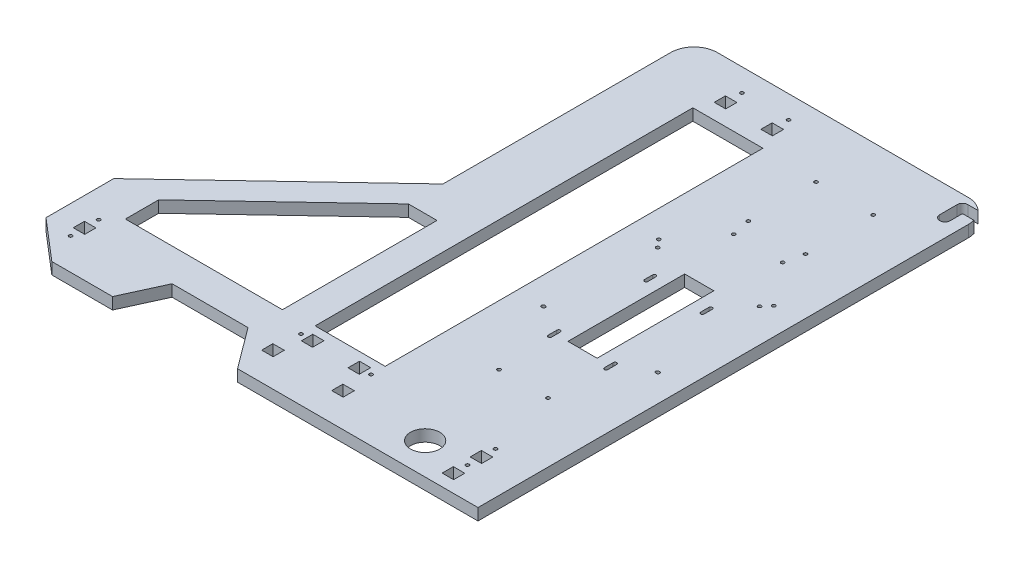
SolidWorks part; units mm, degrees
ref_plane "Front Plane" through (0, 0, 0) normal (0, 0, 1) x (1, 0, 0)
ref_plane "Top Plane" through (0, 0, 0) normal (0, 1, 0) x (1, 0, 0)
ref_plane "Right Plane" through (0, 0, 0) normal (1, 0, 0) x (0, 0, -1)
sketch "Sketch1" plane through (0, 0, 0) normal (0, 1, 0) x (1, 0, 0)
  line L0 (0, 0) -> (-235, 0)
  line L1 (-235, 0) -> (-235, -215)
  line L2 (-235, -215) -> (-380, -352)
  line L3 (-380, -352) -> (-380, -410)
  line L4 (-380, -410) -> (-345, -440)
  line L5 (-345, -440) -> (-293, -440)
  line L6 (-293, -440) -> (-277, -405)
  line L7 (-277, -405) -> (-212, -405)
  line L8 (-212, -405) -> (-185.9255, -440)
  line L9 (-185.9255, -440) -> (0, -440)
  line L10 (0, 0) -> (0, -440)
  line L12 (-293, -440) -> (-185.9255, -440) construction
  dimension "D3" = 235
  dimension "D5" = 58
  dimension "D13" = 190
  dimension "D7" = 35
  dimension "D2" = 126.686
  dimension "D11" = 65
  dimension "D15" = 52
  dimension "D12" = 30
  dimension "D10" = 35
  dimension "D14" = 16
  dimension "D6" = 380
  dimension "D4" = 440
extrude "Boss-Extrude1" add sketch "Sketch1" along normal blind 10
sketch "Sketch16" plane through (0, 10, 0) normal (0, 1, 0) x (1, 0, 0)
  line L0 (0, -440) -> (20, -440)
  line L1 (20, -440) -> (20, 0)
  line L2 (20, 0) -> (0, 0)
  line L3 (0, 0) -> (0, -440)
  dimension "D1" = 20
  dimension "D2" = 90
extrude "Boss-Extrude2" add sketch "Sketch16" against normal through all
sketch "Sketch2" plane through (0, 10, 0) normal (0, 1, 0) x (1, 0, 0)
  line L0 (-235, -215) -> (-235, -405) construction
  line L1 (-277, -405) -> (-212, -405) construction
  line L2 (-345, -440) -> (-345, -318.931) construction
  line L3 (-235, -215) -> (-380, -352) construction
  line L4 (-345, -348.5097) -> (-235, -244.5787)
  line L5 (-235, -244.5787) -> (-210.5, -244.5787)
  line L6 (-210.5, -244.5787) -> (-210.5, -377)
  line L7 (-210.5, -377) -> (-345, -377)
  line L8 (-345, -377) -> (-345, -348.5097)
  line L9 (0, -440) -> (0, 0) construction
  line L10 (-184.5, -375) -> (-124.5, -375)
  line L11 (-184.5, -375) -> (-184.5, -51.45)
  line L12 (-184.5, -51.45) -> (-124.5, -51.45)
  line L13 (-124.5, -375) -> (-124.5, -51.45)
  line L14 (-124.5, -387.1) -> (-184.5, -387.1) construction
  line L15 (-16, -440) -> (-16, 0) construction
  line L16 (20, 0) -> (-235, 0) construction
  line L17 (-355.95, -430.6143) -> (-355.95, -329.2769) construction
  line L18 (-20.9, -429.8) -> (-11.1, -429.8)
  line L19 (-20.9, -429.8) -> (-20.9, -420.2)
  line L20 (-20.9, -420.2) -> (-11.1, -420.2)
  line L21 (-11.1, -429.8) -> (-11.1, -420.2)
  line L22 (-20.9, -429.8) -> (-11.1, -420.2) construction
  line L23 (-20.9, -420.2) -> (-11.1, -429.8) construction
  line L24 (-20.9, -405.8) -> (-11.1, -405.8)
  line L25 (-20.9, -405.8) -> (-20.9, -396.2)
  line L26 (-20.9, -396.2) -> (-11.1, -396.2)
  line L27 (-11.1, -405.8) -> (-11.1, -396.2)
  line L28 (-20.9, -405.8) -> (-11.1, -396.2) construction
  line L29 (-20.9, -396.2) -> (-11.1, -405.8) construction
  line L30 (-380, -410) -> (-345, -440) construction
  line L32 (-351.05, -396.2) -> (-360.85, -396.2)
  line L33 (-351.05, -396.2) -> (-351.05, -405.8)
  line L34 (-351.05, -405.8) -> (-360.85, -405.8)
  line L35 (-360.85, -396.2) -> (-360.85, -405.8)
  line L36 (-351.05, -396.2) -> (-360.85, -405.8) construction
  line L37 (-351.05, -405.8) -> (-360.85, -396.2) construction
  line L38 (-185.9255, -440) -> (20, -440) construction
  line L39 (-185.9255, -440) -> (20, -440) construction
  line L40 (-173.724, -33.45) -> (-113.724, -33.45) construction
  line L41 (-154.5, -51.45) -> (-154.5, -33.45) construction
  line L42 (-179.4, -28.65) -> (-169.6, -28.65)
  line L43 (-179.4, -28.65) -> (-179.4, -38.25)
  line L44 (-179.4, -38.25) -> (-169.6, -38.25)
  line L45 (-169.6, -28.65) -> (-169.6, -38.25)
  line L46 (-179.4, -28.65) -> (-169.6, -38.25) construction
  line L47 (-179.4, -38.25) -> (-169.6, -28.65) construction
  line L48 (-129.6, -38.25) -> (-139.4, -28.65) construction
  line L49 (-129.6, -28.65) -> (-139.4, -38.25) construction
  line L50 (-139.4, -28.65) -> (-139.4, -38.25)
  line L51 (-129.6, -38.25) -> (-139.4, -38.25)
  line L52 (-129.6, -28.65) -> (-129.6, -38.25)
  line L53 (-129.6, -28.65) -> (-139.4, -28.65)
  line L54 (-174.5, -33.45) -> (-174.5, -19.45) construction
  line L55 (-134.5, -33.45) -> (-134.5, -19.45) construction
  line L56 (-154.5, -375) -> (-154.5, -440) construction
  line L57 (-174.5, -387.1) -> (-134.5, -387.1) construction
  line L58 (-129.7, -392) -> (-139.3, -382.2) construction
  line L59 (-179.3, -382.2) -> (-169.7, -382.2)
  line L60 (-179.3, -382.2) -> (-179.3, -392)
  line L61 (-179.3, -392) -> (-169.7, -392)
  line L62 (-169.7, -382.2) -> (-169.7, -392)
  line L63 (-179.3, -382.2) -> (-169.7, -392) construction
  line L64 (-179.3, -392) -> (-169.7, -382.2) construction
  line L65 (-129.7, -382.2) -> (-139.3, -392) construction
  line L66 (-139.3, -382.2) -> (-139.3, -392)
  line L67 (-129.7, -392) -> (-139.3, -392)
  line L68 (-129.7, -382.2) -> (-129.7, -392)
  line L69 (-129.7, -382.2) -> (-139.3, -382.2)
  line L70 (-119.6, -415.9) -> (-129.4, -406.3) construction
  line L71 (-189.4, -406.3) -> (-179.6, -406.3)
  line L72 (-189.4, -406.3) -> (-189.4, -415.9)
  line L73 (-189.4, -415.9) -> (-179.6, -415.9)
  line L74 (-179.6, -406.3) -> (-179.6, -415.9)
  line L75 (-189.4, -406.3) -> (-179.6, -415.9) construction
  line L76 (-189.4, -415.9) -> (-179.6, -406.3) construction
  line L77 (-119.6, -406.3) -> (-129.4, -415.9) construction
  line L78 (-129.4, -406.3) -> (-129.4, -415.9)
  line L79 (-119.6, -415.9) -> (-129.4, -415.9)
  line L80 (-119.6, -406.3) -> (-119.6, -415.9)
  line L81 (-119.6, -406.3) -> (-129.4, -406.3)
  line L82 (-360.85, -396.2) -> (-11.1, -396.2) construction
  circle A0 centre (-16, -413) radius 1.45
  circle A1 centre (-16, -389) radius 1.45
  circle A2 centre (-355.95, -413) radius 1.45
  circle A3 centre (-355.95, -389) radius 1.45
  circle A4 centre (-174.5, -19.45) radius 1.45
  circle A5 centre (-134.5, -19.45) radius 1.45
  circle A6 centre (-124.5, -387.1) radius 1.45
  circle A7 centre (-184.5, -387.1) radius 1.45
  point P25 (-16, -425)
  point P30 (-16, -401)
  point P44 (-355.95, -401)
  point P61 (-174.5, -33.45)
  point P72 (-134.5, -33.45)
  point P85 (-174.5, -387.1)
  point P94 (-134.5, -387.1)
  point P95 (-184.5, -411.1)
  point P104 (-124.5, -411.1)
  point P105 (-154.5, -387.1)
  dimension "D13" = 2.9
  dimension "D14" = 2.9
  dimension "D23" = 2.9
  dimension "D24" = 2.9
  dimension "D31" = 2.9
  dimension "D37" = 2.9
  dimension "D1" = 21.5
  dimension "D2" = 28
  dimension "D3" = 24.5
  dimension "D4" = 60
  dimension "D7" = 26
  dimension "D8" = 9.6
  dimension "D9" = 9.8
  dimension "D10" = 9.8
  dimension "D11" = 9.6
  dimension "D12" = 24
  dimension "D15" = 24
  dimension "D19" = 9.8
  dimension "D20" = 9.6
  dimension "D26" = 12
  dimension "D27" = 9.8
  dimension "D28" = 9.6
  dimension "D33" = 9.6
  dimension "D38" = 9.8
  dimension "D39" = 9.6
  dimension "D41" = 24
  dimension "D34" = 30
  dimension "D36" = 12.1
  dimension "D30" = 18
  dimension "D29" = 40
  dimension "D17" = 15
  dimension "D32" = 14
  dimension "D35" = 20
  dimension "D16" = 12
  dimension "D21" = 90
  dimension "D25" = 24
  dimension "D5" = 353.75
  dimension "D22" = 349.75
  dimension "D40" = 30
  dimension "D6" = 65
  dimension "D42" = 0
  dimension "D43" = 0
  dimension "D18" = 16
  dimension "D44" = 9.8
extrude "Cut-Extrude1" cut sketch "Sketch2" against normal through all
fillet "Fillet1" radius 20 2 edges at (-235, 5, 0) (20, 5, 0)
sketch "Sketch11" plane through (0, 10, 0) normal (0, 1, 0) x (1, 0, 0)
  line L0 (-124.5, -213.225) -> (20, -213.225) construction
  line L1 (20, -440) -> (20, -20) construction
  line L3 (-52.25, -213.225) -> (-52.25, -440) construction
  line L6 (-124.5, -375) -> (-124.5, -51.45) construction
  line L8 (-185.9255, -440) -> (20, -440) construction
  circle A0 centre (-52.25, -413) radius 12.5
  circle A1 centre (-16, -413) radius 1.45 construction
  dimension "D1" = 25
  dimension "D2" = 0
  dimension "D3" = 0
extrude "WiringHole" cut sketch "Sketch11" against normal through all
sketch "Sketch9" [suppressed] plane through (0, 10, 0) normal (0, 1, 0) x (1, 0, 0)
  line L0 (-52.25, -400.5) -> (-52.25, 0) construction
  line L1 (0, 0) -> (-215, 0) construction
  line L2 (-124.5, -213.2375) -> (20, -213.2375) construction
  line L3 (-124.5, -375) -> (-124.5, -51.475) construction
  line L4 (-4.75, -124.7375) -> (-4.75, -301.7375) construction
  line L6 (-99.75, -124.7375) -> (-4.75, -124.7375) construction
  line L7 (-4.75, -301.7375) -> (-99.75, -301.7375) construction
  line L8 (-99.75, -301.7375) -> (-99.75, -124.7375) construction
  line L9 (20, -440) -> (20, -20) construction
  circle A0 centre (-52.25, -413) radius 12.5 construction
  circle A1 centre (-99.75, -124.7375) radius 1.45
  circle A2 centre (-4.75, -124.7375) radius 1.45
  circle A3 centre (-4.75, -301.7375) radius 1.45
  circle A4 centre (-99.75, -301.7375) radius 1.45
  dimension "D3" = 2.9
  dimension "D4" = 2.9
  dimension "D1" = 95
  dimension "D2" = 177
  dimension "D5" = 47.5
extrude "MountingHoles-PSU" [suppressed] cut sketch "Sketch9" against normal through all
sketch "Sketch10" plane through (0, 10, 0) normal (0, 1, 0) x (1, 0, 0)
  line L0 (-124.5, -213.225) -> (20, -213.225) construction
  line L1 (20, -440) -> (20, -20) construction
  line L2 (-64.75, -228.225) -> (-39.75, -228.225) construction
  line L3 (-52.25, -213.225) -> (-52.25, 0) construction
  line L7 (-124.5, -375) -> (-124.5, -51.45) construction
  line L8 (-64.75, -278.225) -> (-39.75, -278.225)
  line L9 (-64.75, -278.225) -> (-64.75, -178.225)
  line L10 (-64.75, -178.225) -> (-39.75, -178.225)
  line L11 (-39.75, -278.225) -> (-39.75, -178.225)
  line L12 (-64.75, -278.225) -> (-39.75, -178.225) construction
  line L13 (-64.75, -178.225) -> (-39.75, -278.225) construction
  line L15 (0, 0) -> (-215, 0) construction
  line L17 (-52.25, -213.225) -> (-52.25, -440) construction
  line L18 (-185.9255, -440) -> (20, -440) construction
  line L19 (-64.75, -213.225) -> (-39.75, -213.225) construction
  line L20 (-52.25, -278.225) -> (-52.25, -178.225) construction
  dimension "D1" = 25
  dimension "D2" = 100
  dimension "D3" = 0
  dimension "D4" = 0
  dimension "D5" = 0
  dimension "D6" = 15
extrude "WiringSlot" cut sketch "Sketch10" against normal through all
sketch "CenterLines" plane through (0, 10, 0) normal (0, 1, 0) x (1, 0, 0)
  line L0 (-52.25, -278.225) -> (-52.25, -178.225) construction
  line L1 (-64.75, -278.225) -> (-39.75, -278.225) construction
  line L2 (-39.75, -178.225) -> (-64.75, -178.225) construction
  line L3 (-64.75, -228.225) -> (-39.75, -228.225) construction
  line L4 (-64.75, -178.225) -> (-64.75, -278.225) construction
  line L5 (-39.75, -278.225) -> (-39.75, -178.225) construction
ref_plane "Plane1" through (-52.25, 0, 0) normal (1, 0, 0) x (0, 0, -1)
sketch "Sketch6" plane through (0, 10, 0) normal (0, 1, 0) x (1, 0, 0)
  line L0 (-52.25, -278.225) -> (-52.25, -178.225) construction
  line L1 (-76.35, -237.075) -> (-28.15, -237.075) construction
  line L2 (-28.15, -192.625) -> (-28.15, -275.125) construction
  line L3 (-64.75, -278.225) -> (-39.75, -278.225) construction
  line L4 (-64.75, -245.925) -> (-39.75, -245.925) construction
  line L5 (-39.75, -178.225) -> (-64.75, -178.225) construction
  line L6 (-28.15, -192.625) -> (-28.15, -199.625) construction
  line L7 (-26.7, -192.625) -> (-26.7, -199.625)
  line L8 (-29.6, -192.625) -> (-29.6, -199.625)
  line L9 (-64.75, -228.225) -> (-39.75, -228.225) construction
  line L10 (-64.75, -178.225) -> (-64.75, -278.225) construction
  line L11 (-39.75, -278.225) -> (-39.75, -178.225) construction
  line L12 (-28.15, -282.125) -> (-28.15, -275.125) construction
  line L13 (-29.6, -282.125) -> (-29.6, -275.125)
  line L14 (-76.35, -274.525) -> (-76.35, -199.625) construction
  line L15 (-28.15, -282.125) -> (-28.15, -199.625) construction
  line L16 (-26.7, -282.125) -> (-26.7, -275.125)
  arc A2 (-26.7, -192.625) -> (-29.6, -192.625) centre (-28.15, -192.625) ccw
  arc A3 (-29.6, -199.625) -> (-26.7, -199.625) centre (-28.15, -199.625) ccw
  circle A4 centre (-76.35, -274.525) radius 1.45
  circle A6 centre (-76.35, -199.625) radius 1.45
  arc A8 (-29.6, -282.125) -> (-26.7, -282.125) centre (-28.15, -282.125) ccw
  arc A9 (-26.7, -275.125) -> (-29.6, -275.125) centre (-28.15, -275.125) ccw
  point P20 (-28.15, -196.125)
  point P25 (-28.15, -278.625)
  dimension "D8" = 2.9
  dimension "D12" = 2.9
  dimension "D4" = 1.45
  dimension "D5" = 1.45
  dimension "D11" = 82.5
  dimension "D14" = 74.9
  dimension "D2" = 24.1
  dimension "D3" = 48.2
  dimension "D6" = 8.85
  dimension "D9" = 7
  dimension "D10" = 7
extrude "MountingHoles-RAMPS" cut sketch "Sketch6" against normal through all
mirror "Mirror1" about plane through (-52.25, 0, 0) normal (1, 0, 0) of "MountingHoles-RAMPS"
sketch "Sketch5" plane through (0, 10, 0) normal (0, 1, 0) x (1, 0, 0)
  line L0 (-39.75, -228.225) -> (-64.75, -228.225) construction
  line L3 (-39.75, -278.225) -> (-39.75, -178.225) construction
  line L5 (-64.75, -178.225) -> (-64.75, -278.225) construction
  line L7 (-31.25, -127.725) -> (-73.25, -127.725) construction
  line L8 (-31.25, -328.725) -> (-73.25, -328.725) construction
  line L9 (-52.25, -228.225) -> (-52.25, -127.725) construction
  line L10 (-52.25, -228.225) -> (-52.25, -328.725) construction
  circle A0 centre (-73.25, -127.725) radius 1.45
  circle A1 centre (-31.25, -127.725) radius 1.45
  circle A2 centre (-31.25, -328.725) radius 1.45
  circle A3 centre (-73.25, -328.725) radius 1.45
  point P17 (-52.25, -127.725)
  point P22 (-52.25, -328.725)
  dimension "D2" = 2.9
  dimension "D5" = 2.9
  dimension "D6" = 2.9
  dimension "D7" = 2.9
  dimension "D3" = 201
  dimension "D4" = 100.5
  dimension "D8" = 21
  dimension "D9" = 21
  dimension "D10" = 100.5
extrude "MountingHoles-Melzi" cut sketch "Sketch5" against normal through all
sketch "Sketch13" plane through (0, 0, 0) normal (0, -1, 0) x (-1, 0, 0)
  line L0 (64.75, -213.225) -> (124.5, -213.225) construction
  line L1 (124.5, -375) -> (124.5, -51.45) construction
  line L2 (101.46, -262.74) -> (101.46, -163.71) construction
  line L3 (52.25, -278.225) -> (52.25, -178.225) construction
  line L4 (64.75, -178.225) -> (64.75, -278.225) construction
  line L6 (101.46, -262.74) -> (3.56, -262.74) construction
  circle A0 centre (101.46, -163.71) radius 1.45
  circle A1 centre (101.46, -262.74) radius 1.45
  circle A2 centre (8.62, -170.19) radius 1.45
  circle A3 centre (3.56, -262.74) radius 1.45
  point P11 (101.46, -213.225)
  dimension "D8" = 2.9
  dimension "D6" = 2.9
  dimension "D1" = 2.9
  dimension "D2" = 49.515
  dimension "D3" = 49.21
  dimension "D4" = 6.48
  dimension "D5" = 92.84
  dimension "D7" = 97.9
extrude "Mountingholes-Smoothieboard" cut sketch "Sketch13" against normal through all
mirror "Flipped" about plane through (-52.25, 0, 0) normal (1, 0, 0) of "Mountingholes-Smoothieboard"
sketch "Sketch21" plane through (0, 10, 0) normal (0, 1, 0) x (1, 0, 0)
  line L0 (-52.25, -178.225) -> (-52.25, 0) construction
  line L1 (-39.75, -178.225) -> (-64.75, -178.225) construction
  line L2 (0, 0) -> (-215, 0) construction
  line L3 (-52.25, -82.725) -> (-23.3697, -82.725) construction
  circle A0 centre (-27.75, -53.725) radius 1.45
  circle A1 centre (-76.75, -53.725) radius 1.45
  circle A2 centre (-76.75, -111.725) radius 1.45
  circle A3 centre (-27.75, -111.725) radius 1.45
  circle A4 centre (-31.25, -127.725) radius 1.45 construction
  dimension "D1" = 2.9
  dimension "D2" = 24.5
  dimension "D3" = 29
  dimension "D4" = 45
extrude "Pi" cut sketch "Sketch21" against normal through all
sketch "Sketch17" plane through (0, 10, 0) normal (0, 1, 0) x (1, 0, 0)
  line L0 (0, 0) -> (20, 0) construction
  line L1 (20, -23.6361) -> (20, 0) construction
  line L2 (20, -440) -> (20, -20) construction
  line L3 (20, -10) -> (5, -10) construction
  line L4 (20, -14.5) -> (5, -14.5)
  line L5 (20, -5.5) -> (5, -5.5)
  arc A0 (20, -14.5) -> (20, -5.5) centre (20, -10) ccw
  arc A1 (5, -5.5) -> (5, -14.5) centre (5, -10) ccw
  point P8 (12.5, -10)
  dimension "D1" = 9
  dimension "D2" = 15
  dimension "D3" = 10
extrude "Cut-Extrude3" cut sketch "Sketch17" against normal through all
sketch "Sketch18" plane through (0, 10, 0) normal (0, 1, 0) x (1, 0, 0)
  line L0 (5, -5.5) -> (5, -14.5) construction
  line L1 (0.5, -10) -> (5, -10) construction
  line L2 (5, -10) -> (5, -25) construction
  line L3 (9.5, -10) -> (9.5, -25)
  line L4 (0.5, -10) -> (0.5, -25)
  arc A0 (5, -5.5) -> (5, -14.5) centre (5, -10) ccw construction
  arc A1 (9.5, -10) -> (0.5, -10) centre (5, -10) ccw
  arc A2 (0.5, -25) -> (9.5, -25) centre (5, -25) ccw
  point P10 (5, -17.5)
  dimension "D1" = 9
  dimension "D2" = 0
  dimension "D3" = 15
extrude "Cut-Extrude4" cut sketch "Sketch18" against normal through all
sketch "Sketch19" plane through (0, 10, 0) normal (0, 1, 0) x (1, 0, 0)
  line L0 (-5, -25) -> (15, -25) construction
  line L1 (5, -25) -> (5, -5.5) construction
  circle A0 centre (15, -25) radius 1.45
  arc A1 (5, -5.5) -> (0.5, -10) centre (5, -10) ccw construction
  circle A2 centre (-5, -25) radius 1.45
  dimension "D2" = 2.9
extrude "Cut-Extrude5" [suppressed] cut sketch "Sketch19" against normal through all
equation "\"Y-ROD-SPACING\"=75"
equation "\"Y-BED-OFFSET\"=2"
equation "\"Y-BED-ROD-INSET\"=3.5"
equation "\"T-SLOT-NUT-FILLET-RADIUS\"=0.5"
equation "\"T-SLOT-SCREW-SHAFT-RADIUS\"=1.55"
equation "\"T-SLOT-SCREW-SHAFT-CUTOUT-LENGTH\"=11.0"
equation "\"T-SLOT-NUT-DEPTH\"=3.5"
equation "\"T-SLOT-NUT-WIDTH\"=2.85"
equation "\"T-SLOT-NUT-END-DISTANCE\"=8"
equation "\"ACRYLIC-TAB-CUTOUT-SIZE\"=\"ACRYLIC-THICKNESS\"+\"ACRYLIC-TAB-TOLERANCE\"*2"
equation "\"ACRYLIC-TAB-WIDTH\"=\"ACRYLIC-THICKNESS\""
equation "\"ACRYLIC-M3-HOLE\"=2.9"
equation "\"SMOOTHROD-CAP-SCREW-DISTANCE\"=20"
equation "\"FRAME-WIDTH-INNER\"=370"
equation "\"D24@Sketch2\"=\"ACRYLIC-M3-HOLE\""
equation "\"D23@Sketch2\"=\"ACRYLIC-M3-HOLE\""
equation "\"D19@Sketch2\"=\"ACRYLIC-THICKNESS\"-\"KERF\"*2"
equation "\"D20@Sketch2\"=\"ACRYLIC-TAB-WIDTH\"-\"KERF\"*4"
equation "\"D37@Sketch2\"=\"ACRYLIC-M3-HOLE\""
equation "\"D33@Sketch2\"=\"ACRYLIC-TAB-WIDTH\"-\"KERF\"*4"
equation "\"D38@Sketch2\"=\"ACRYLIC-THICKNESS\"-\"KERF\"*2"
equation "\"D39@Sketch2\"=\"ACRYLIC-TAB-WIDTH\"-\"KERF\"*4"
equation "\"D13@Sketch2\"=\"ACRYLIC-M3-HOLE\""
equation "\"D14@Sketch2\"=\"ACRYLIC-M3-HOLE\""
equation "\"D8@Sketch2\"=\"ACRYLIC-TAB-WIDTH\"-\"KERF\"*4"
equation "\"D9@Sketch2\"=\"ACRYLIC-THICKNESS\"-\"KERF\"*2"
equation "\"D10@Sketch2\"=\"ACRYLIC-THICKNESS\"-\"KERF\"*2"
equation "\"D11@Sketch2\"=\"ACRYLIC-TAB-WIDTH\"-\"KERF\"*4"
equation "\"D31@Sketch2\"=\"ACRYLIC-M3-HOLE\""
equation "\"D27@Sketch2\"=\"ACRYLIC-THICKNESS\"-\"KERF\"*2"
equation "\"D28@Sketch2\"=\"ACRYLIC-TAB-WIDTH\"-\"KERF\"*4"
equation "\"NEMA17-HOLE-SPACING\"=31"
equation "\"NEMA17-CENTRAL-CUTOUT\"=22.5"
equation "\"Z-BRACKET-REACH\"=55"
equation "\"TOP-BRACKET-SPACING\"=40"
equation "\"D29@Sketch2\"=\"TOP-BRACKET-SPACING\""
equation "\"ACRYLIC-THICKNESS\"=10"
equation "\"SMOOTHROD-Z-LENGTH\"=350"
equation "\"D5@Sketch2\"=\"SMOOTHROD-Z-LENGTH\"-\"SMOOTHROD-TIGHTENING-HEADROOM\"+4"
equation "\"SMOOTHROD-X-LENGTH\"=350"
equation "\"SMOOTHROD-Y-LENGTH\"=350"
equation "\"D22@Sketch2\"=\"SMOOTHROD-Y-LENGTH\"-\"SMOOTHROD-TIGHTENING-HEADROOM\""
equation "\"SMOOTHROD-TIGHTENING-HEADROOM\"=.25"
equation "\"X-ROD-SPACING\"=45"
equation "\"Z-ROD-SPACING\"=17.5"
equation "\"LEADSCREW-Z-LENGTH\"=300"
equation "\"SCREW-HEAD-RADIUS\"=6"
equation "\"PRINTED-X-SMOOTHROD-DIAMETER\"=9.0"
equation "\"PRINTED-X-SMOOTHROD-CUTOUT\"=10"
equation "\"PRINTED-X-BASE-HEIGHT\"=10"
equation "\"PRINTED-LM8UU-CUTOUT-SIZE\"=15.5"
equation "\"PRINTED-LM8UU-CUTOUT-LENGTH\"=24.5"
equation "\"PRINTED-X-IDLER-HEIGHT\"=16"
equation "\"PSU-MOUNTING-WIDTH\"=95"
equation "\"PSU-MOUNTING-HEIGHT\"=177"
equation "\"D1@Sketch9\"=\"PSU-MOUNTING-WIDTH\""
equation "\"D3@Sketch9\"=\"ACRYLIC-M3-HOLE\""
equation "\"D1@Boss-Extrude1\"=\"ACRYLIC-THICKNESS\""
equation "\"D6@Sketch1\"=\"SMOOTHROD-Y-LENGTH\"+30"
equation "\"D4@Sketch9\"=\"ACRYLIC-M3-HOLE\""
equation "\"D2@Sketch9\"=\"PSU-MOUNTING-HEIGHT\""
equation "\"D5@Sketch9\"=\"PSU-MOUNTING-WIDTH\"/2"
equation "\"D4@Sketch1\"=\"SMOOTHROD-Z-LENGTH\"+90"
equation "\"D8@Sketch6\"=\"ACRYLIC-M3-HOLE\""
equation "\"D12@Sketch6\"=\"ACRYLIC-M3-HOLE\""
equation "\"D2@Sketch5\"=\"ACRYLIC-M3-HOLE\""
equation "\"D5@Sketch5\"=\"ACRYLIC-M3-HOLE\""
equation "\"D6@Sketch5\"=\"ACRYLIC-M3-HOLE\""
equation "\"D7@Sketch5\"=\"ACRYLIC-M3-HOLE\""
equation "\"D1@Sketch13\"=\"ACRYLIC-M3-HOLE\""
equation "\"D6@Sketch13\"=\"ACRYLIC-M3-HOLE\""
equation "\"D8@Sketch13\"=\"ACRYLIC-M3-HOLE\""
equation "\"D4@Sketch6\"=\"ACRYLIC-M3-HOLE\"/2"
equation "\"D5@Sketch6\"=\"ACRYLIC-M3-HOLE\"/2"
equation "\"Y-BED-SCREW-SPACING\"=209"
equation "\"Y-BED-SCREW-CUTOUT-SLOT-HEIGHT\"=2"
equation "\"ACRYLIC-THICKNESS2\"=4.5"
equation "\"ACRYLIC-TAB-TOLERANCE\"=-.05"
equation "\"Z-ROD-INSET\"=16"
equation "\"SCREW-LENGTH-FRAME\"=\"ACRYLIC-THICKNESS\" + 10"
equation "\"SCREW-LENGTH-MOTOR\"=\"ACRYLIC-THICKNESS\" + 5"
equation "\"SCREW-LENGTH-EXTRUDER\"=28"
equation "\"Y-BELT-TO-ROD-DISTANCE\"=20"
equation "\"SPOOL-HOLDER-ROD-SPACING\"=150"
equation "\"ACRYLIC-X-CARRIAGE-WIDTH\"=55"
equation "\"ACRYLIC-X-CARRIAGE-HEIGHT\"=75"
equation "\"ACRYLIC-X-CARRIAGE-LM8UU-CUTOUT-WIDTH\"=24.25"
equation "\"ACRYLIC-X-CARRIAGE-SCREW-SPACING-X\"=15"
equation "\"ACRYLIC-X-CARRIAGE-SCREW-SPACING-Y\"=33"
equation "\"ACRYLIC-X-CARRIAGE-CENTER-TAB-SPACING\"=14"
equation "\"ACRYLIC-X-CARRIAGE-EXTRUDER-OFFSET\"=26"
equation "\"ACRYLIC-X-CARRIAGE-EXTRUDER-ANGLE\"=90"
equation "\"ACRYLIC-X-CARRIAGE-EXTRUDER-SHELF-DEPTH\"=\"ACRYLIC-X-CARRIAGE-EXTRUDER-OFFSET\" + 28"
equation "\"ACRYLIC-X-CARRIAGE-EXTRUDER-BRACE-SPACING\"=23"
equation "\"ACRYLIC-X-CARRIAGE-EXTRUDER-BRACE-TAB-OFFSET\"=20"
equation "\"ACRYLIC-X-CARRIAGE-EXTRUDER-BRACE-HEIGHT\"=35"
equation "\"ACRYLIC-X-CARRIAGE-EXTRUDER-BRACE-SCREW-SPACING\"=22"
equation "\"D1@Sketch19\"=\"SMOOTHROD-CAP-SCREW-DISTANCE\"/2"
equation "\"D2@Sketch19\"=\"ACRYLIC-M3-HOLE\""
equation "\"D1@Sketch21\"=\"ACRYLIC-M3-HOLE\""
equation "\"KERF\"=0.1"
equation "\"PRINTED-M3-HOLE\"=3.5"
equation "\"PRINTED-M3-NUT-AF\"=6.25"
equation "\"ACRYLIC-X-CARRIAGE-LM8UU-CUTOUT-HEIGHT\"=11.0"
equation "\"ACRYLIC-X-CARRIAGE-DUAL-WIDTH-MULTIPLIER\"=1.65"
equation "\"ACRYLIC-X-CARRIAGE-DUAL-HOTEND-SPACING\"=42"
equation "\"ACRYLIC-X-CARRIAGE-DUAL-WIDTH\"=75"
equation "\"ACRYLIC-X-CARRIAGE-DUAL-FAN-OFFSET\"=52"
equation "\"ACRYLIC-X-CARRIAGE-DUAL-FAN-HEIGHT\"=20"
equation "\"ACRYLIC-X-CARRIAGE-DUAL-HOTEND-SEPARATION\"=36"
equation "\"ACRYLIC-X-CARRIAGE-DUAL-MOUNT-PLATE-DEPTH\"=75"
equation "\"ACRYLIC-X-CARRIAGE-DUAL-MOUNT-BRACE-WIDTH\"=33"
equation "\"ACRYLIC-X-CARRIAGE-DUAL-MOUNT-SCREW-WIDTH\"=40"
equation "\"BLOWER-FAN-WIDTH\"=15"
equation "\"D44@Sketch2\"=\"ACRYLIC-THICKNESS\"-\"KERF\"*2"
